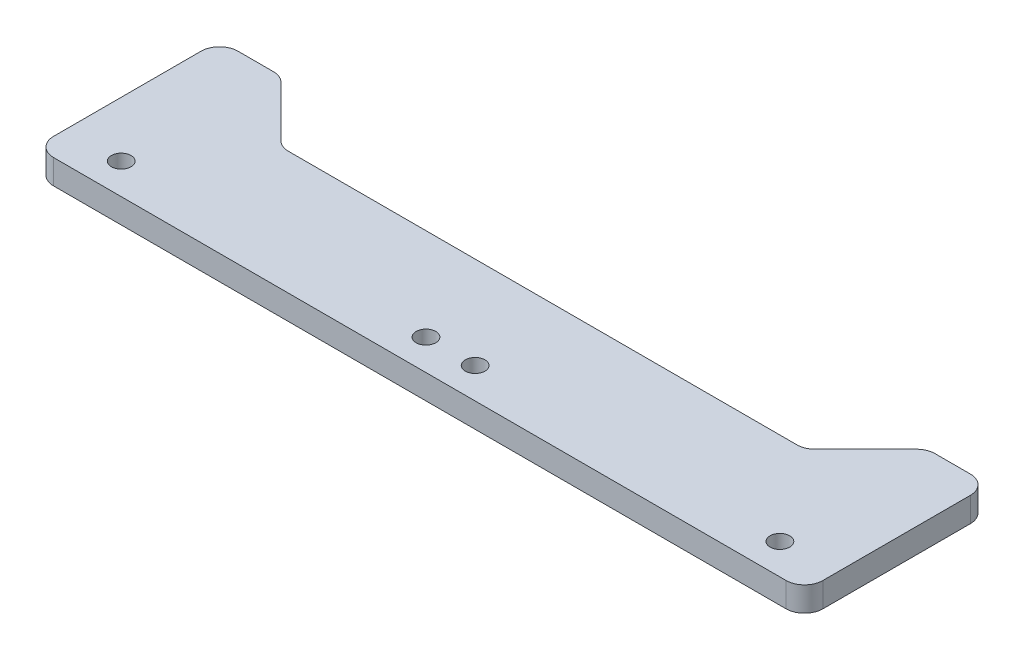
SolidWorks part; units mm, degrees
ref_plane "前视基准面" through (0, 0, 0) normal (0, 0, 1) x (1, 0, 0)
ref_plane "上视基准面" through (0, 0, 0) normal (0, 1, 0) x (1, 0, 0)
ref_plane "右视基准面" through (0, 0, 0) normal (1, 0, 0) x (0, 0, -1)
sketch "草图1" plane through (0, 0, 0) normal (0, 1, 0) x (1, 0, 0)
  line L0 (-62.6, 15) -> (-52.6, 15)
  line L1 (-42.6, 5) -> (42.6, 5)
  line L2 (-62.6, 15) -> (-62.6, -15)
  line L3 (-62.6, -15) -> (62.6, -15)
  line L4 (62.6, 15) -> (62.6, -15)
  line L9 (-52.6, 15) -> (-42.6, 5)
  line L10 (62.6, 15) -> (52.6, 15)
  line L11 (52.6, 15) -> (42.6, 5)
  point P0 (0, 0)
  dimension "D1" = 125.2
  dimension "D2" = 30
  dimension "D3" = 10
  dimension "D4" = 10
extrude "凸台-拉伸2" add sketch "草图1" along normal blind 4
sketch "草图6" plane through (0, 4, 0) normal (0, 1, 0) x (1, 0, 0)
  line L0 (0, 5) -> (0, -15) construction
  line L1 (42.6, 5) -> (-42.6, 5) construction
  line L2 (-62.6, -15) -> (62.6, -15) construction
  line L3 (-62.6, 15) -> (-62.6, -15) construction
  circle A0 centre (-53.6, -10) radius 1.6
  circle A1 centre (-4, -10) radius 1.6
  circle A2 centre (4, -10) radius 1.6
  circle A3 centre (53.6, -10) radius 1.6
  dimension "D1" = 5
  dimension "D3" = 4
  dimension "D4" = 5
  dimension "D5" = 3.2
  dimension "D6" = 3.2
  dimension "D2" = 9
extrude "切除-拉伸2" cut sketch "草图6" against normal blind 4
fillet "圆角2" radius 3 8 edges at (62.6, 2, 15) (-62.6, 2, 15) (-52.6, 2, -15) (-42.6, 2, -5) (42.6, 2, -5) (52.6, 2, -15) (62.6, 2, -15) (-62.6, 2, -15) first distance on face at (0, 2, 15) first distance on face at (-57.6, 2, -15) first distance on face at (0, 2, -5) first distance on face at (57.6, 2, -15)
